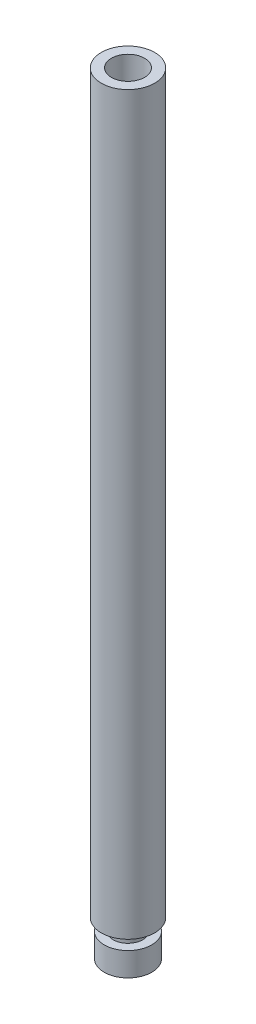
SolidWorks part; units mm, degrees
ref_plane "Front Plane" through (0, 0, 0) normal (0, 0, 1) x (1, 0, 0)
ref_plane "Top Plane" through (0, 0, 0) normal (0, 1, 0) x (1, 0, 0)
ref_plane "Right Plane" through (0, 0, 0) normal (1, 0, 0) x (0, 0, -1)
sketch "Sketch1" plane through (0, 0, 0) normal (0, 1, 0) x (1, 0, 0)
  circle A0 centre (-0.522, 0.5111) radius 1.375
  circle A1 centre (-0.522, 0.5111) radius 2.25
  dimension "D1" = 2.75
  dimension "D2" = 4.5
extrude "Boss-Extrude1" add sketch "Sketch1" along normal blind 62 contours A1
extrude "Boss-Extrude2" add sketch "Sketch1<3>" along normal blind 1 contours A0 region at (-0.522, 0, -0.5111)
sketch "Sketch1<3>" plane through (0, 0, 0) normal (0, 1, 0) x (1, 0, 0) same geometry as "Sketch1"
sketch "Sketch5" plane through (0, 0, 0) normal (0, -1, 0) x (1, 0, 0)
  circle A3 centre (-0.522, -0.5111) radius 1.25
  dimension "D1" = 2.5
extrude "Boss-Extrude3" add sketch "Sketch5" along normal blind 1 contours A3
sketch "Sketch6" plane through (0, -1, 0) normal (0, -1, 0) x (1, 0, 0)
  circle A0 centre (-0.522, -0.5111) radius 2
  dimension "D1" = 4
extrude "Boss-Extrude4" add sketch "Sketch6" along normal blind 2
sketch "Sketch8" plane through (0, -3, 0) normal (0, -1, 0) x (-1, 0, 0)
  circle A0 centre (0.522, 0.5111) radius 1.5
  dimension "D1" = 3
sketch "Sketch11" plane through (0, 62, 0) normal (0, 1, 0) x (1, 0, 0)
  text T0 "VIII" font "Century Gothic" height in points 5
sketch "Sketch12" plane through (0, 62, 0) normal (0, 1, 0) x (1, 0, 0)
  circle A0 centre (-0.522, 0.5111) radius 1.4
  dimension "D1" = 2.8
extrude "Cut-Extrude1" cut sketch "Sketch12" against normal blind 15
